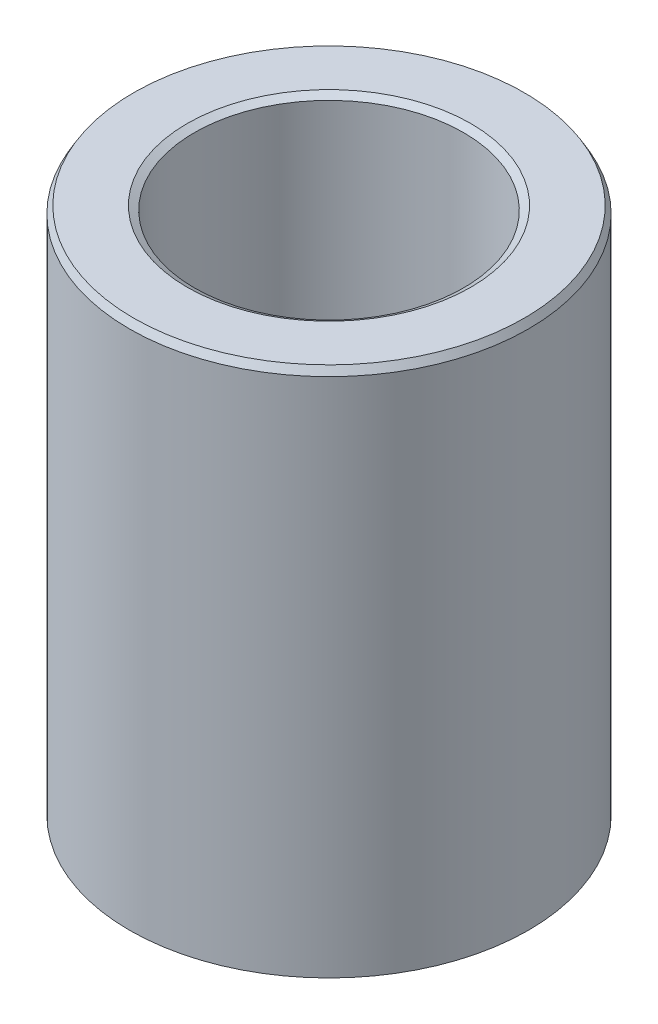
SolidWorks part; units mm, degrees
ref_plane "Front Plane" through (0, 0, 0) normal (0, 0, 1) x (1, 0, 0)
ref_plane "Top Plane" through (0, 0, 0) normal (0, 1, 0) x (1, 0, 0)
ref_plane "Right Plane" through (0, 0, 0) normal (1, 0, 0) x (0, 0, -1)
sketch "Sketch1" plane through (0, 0, 0) normal (0, 1, 0) x (1, 0, 0)
  circle A0 centre (0, 0) radius 7.5
  dimension "SLEEVE_OD" = 15
extrude "Boss-Extrude1" add sketch "Sketch1" along normal blind 20.0077
sketch "Sketch2" plane through (0, 0, 0) normal (0, 1, 0) x (1, 0, 0)
  circle A0 centre (0, 0) radius 5.0597
  dimension "BORE_D" = 10.1193
extrude "Cut-Extrude1" cut sketch "Sketch2" along normal through all
chamfer "Chamfer1" distance 0.2728 angle 30 4 edges at (0, 20.0077, 5.0597) (0, 0, 5.0597) (0, 0, 7.5) (0, 20.0077, 7.5) first distance on face at (0, 20.0077, 5.0597) first distance on face at (0, 0, 5.0597) first distance on face at (0, 20.0077, 7.5)
